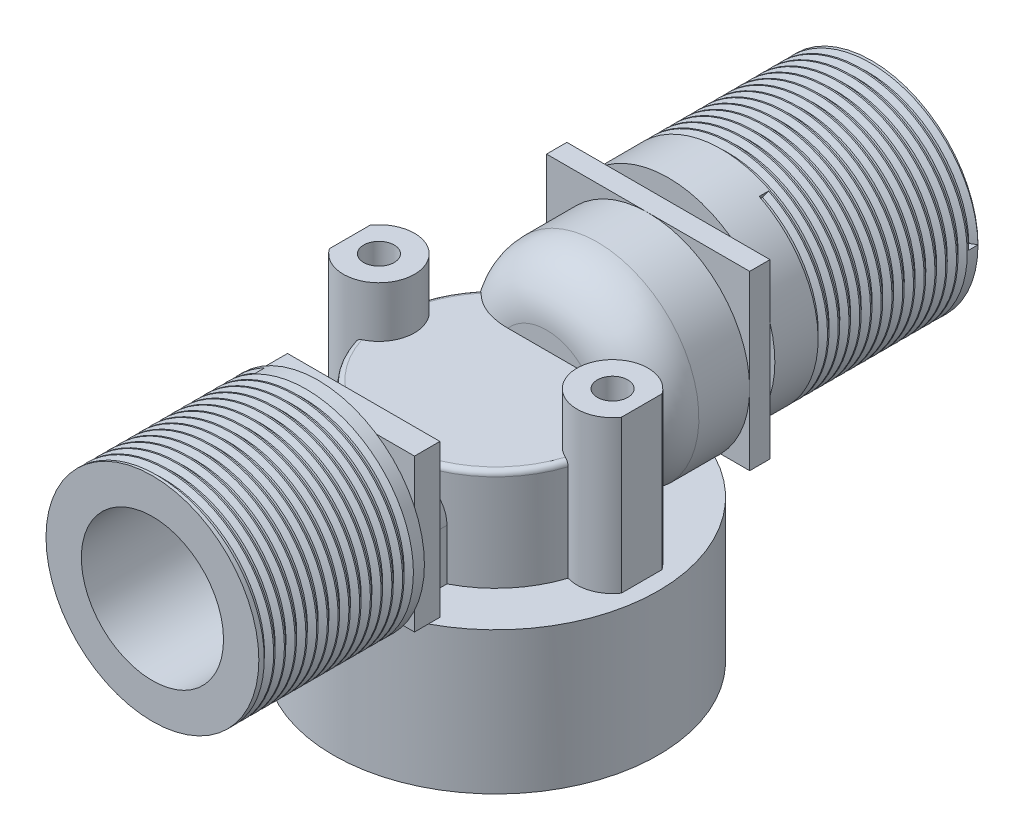
SolidWorks part; units mm, degrees
ref_plane "Спереди" through (0, 0, 0) normal (0, 0, 1) x (1, 0, 0)
ref_plane "Сверху" through (0, 0, 0) normal (0, 1, 0) x (1, 0, 0)
ref_plane "Справа" through (0, 0, 0) normal (1, 0, 0) x (0, 0, -1)
sketch "Эскиз1" plane through (0, 0, 0) normal (0, 1, 0) x (1, 0, 0)
  circle A0 centre (0, 0) radius 16
  dimension "D1" = 32
extrude "Бобышка-Вытянуть1" add sketch "Эскиз1" along normal blind 14
sketch "Эскиз2" plane through (0, 14, 0) normal (0, 1, 0) x (1, 0, 0)
  circle A0 centre (0, 0) radius 11
  dimension "D1" = 22
extrude "Бобышка-Вытянуть2" add sketch "Эскиз2" along normal blind 10
sketch "Эскиз3" plane through (0, 14, 0) normal (0, 1, 0) x (1, 0, 0)
  line L0 (0, 13.8685) -> (0, -18.4575) construction
  circle A0 centre (11.5, 0) radius 3.5
  circle A1 centre (-11.5, 0) radius 3.5
extrude "Бобышка-Вытянуть3" add sketch "Эскиз3" along normal blind 15
sketch "Эскиз4" plane through (0, 29, 0) normal (0, 1, 0) x (1, 0, 0)
  line L0 (-14.3723, 2) -> (-14.3723, -2)
  line L1 (0, 11) -> (0, -11) construction
  line L2 (14.3723, 2) -> (14.3723, -2)
  circle A0 centre (-11.5, 0) radius 1.5
  circle A1 centre (11.5, 0) radius 1.5
  arc A2 (-14.3723, 2) -> (-14.3723, -2) centre (-11.5, 0) ccw
  arc A3 (10.4783, 3.3475) -> (-10.4783, 3.3475) centre (0, 0) ccw construction
  arc A4 (-10.4783, -3.3475) -> (10.4783, -3.3475) centre (0, 0) ccw construction
  arc A6 (-14.3723, 2) -> (-14.3723, -2) centre (-11.5, 0) ccw
  arc A9 (14.3723, 2) -> (14.3723, -2) centre (11.5, 0) cw
  circle M1 centre (-11.5, 0) radius 3.5
  dimension "D1" = 4
extrude "Вырез-Вытянуть1" cut sketch "Эскиз4" against normal blind 15 contours L0 M1 | A0 | A1 | A9 L2 region at (-14.6254, 29, 0) region at (14.6254, 29, 0) region at (-11.5, 29, 0) region at (11.5, 29, 0)
sketch "Эскиз5" plane through (0, 0, 0) normal (0, 0, 1) x (1, 0, 0)
  line L0 (10.4783, 24) -> (-10.4783, 24) construction
  line L1 (-5, 19) -> (-5, 14)
  line L2 (-5, 14) -> (5, 14)
  line L3 (5, 14) -> (5, 19)
  arc A0 (5, 19) -> (-5, 19) centre (0, 19) ccw
  dimension "D1" = 10
extrude "Бобышка-Вытянуть8" add sketch "Эскиз5" along normal blind 13
sketch "Эскиз6" plane through (0, 0, 13) normal (0, 0, 1) x (1, 0, 0)
  line L1 (16, 14) -> (-16, 14) construction
  line L2 (-7.5, 29) -> (7.5, 29)
  line L3 (7.5, 29) -> (7.5, 14)
  line L4 (7.5, 14) -> (-7.5, 14)
  line L5 (-7.5, 14) -> (-7.5, 29)
  dimension "D1" = 15
  dimension "D2" = 15
extrude "Бобышка-Вытянуть9" add sketch "Эскиз6" along normal blind 2.5
sketch "Эскиз7" plane through (0, 0, 15.5) normal (0, 0, 1) x (1, 0, 0)
  line L0 (7.5, 29) -> (-7.5, 29) construction
  circle A0 centre (0, 22.25) radius 6.5
  dimension "D1" = 6.75
extrude "Бобышка-Вытянуть10" add sketch "Эскиз7" along normal blind 2
sketch "Эскиз41" plane through (0, 0, 17.5) normal (0, 0, 1) x (1, 0, 0)
  circle A0 centre (0, 22.25) radius 10.4775
  dimension "D1" = 20.955
extrude "Бобышка-Вытянуть19" add sketch "Эскиз41" along normal blind 16.3
ref_plane "Плоскость1" through (0, 0, -17) normal (0, 0, 1) x (1, 0, 0)
sketch "Эскиз35" plane through (0, 0, -17) normal (0, 0, 1) x (1, 0, 0)
  line L0 (-10, 30.75) -> (10, 30.75)
  line L1 (10, 30.75) -> (10, 13.75)
  line L2 (10, 13.75) -> (-10, 13.75)
  line L3 (-10, 13.75) -> (-10, 30.75)
  dimension "D1" = 17
  dimension "D2" = 20
extrude "Бобышка-Вытянуть17" add sketch "Эскиз35" along normal blind 2
sketch "Эскиз36" plane through (0, 0, -15) normal (0, 0, 1) x (1, 0, 0)
  circle A0 centre (0, 20.75) radius 10
  dimension "D1" = 20
extrude "Бобышка-Вытянуть18" add sketch "Эскиз36" along normal blind 10
fillet "Скругление1" radius 5 1 edges at (0, 30.75, -5)
sketch "Эскиз40" plane through (0, 0, 0) normal (0, -1, 0) x (1, 0, 0)
  line L0 (-7.6613, 0) -> (6.2158, 0)
  line L1 (0, 0) -> (0, 8.1557)
sketch "Эскиз42" plane through (0, 0, -17) normal (0, 0, -1) x (-1, 0, 0)
  circle A0 centre (0, 22.25) radius 10.4775
  dimension "D1" = 20.955
extrude "Бобышка-Вытянуть20" add sketch "Эскиз42" along normal blind 20
fillet "Скругление2" radius 0.5 4 edges at (-6.4876, 24, 8.8832) (6.4876, 24, 8.8832) (-9.6382, 24, -5.3014) (9.6382, 24, -5.3014)
thread "Резьба1" pitch 1.0583 method cut profile "Профиль резьбы1" start angle 0, offset 0, length 15, pitch 1.0583, diameter 20.955
ref_plane "Плоскость2" through (-10.4775, 22.25, 33.8) normal (0, -1, 0) x (-1, 0, 0)
sketch "Профиль резьбы1" plane through (-10.4775, 22.25, 33.8) normal (0, -1, 0) x (-1, 0, 0)
  line L0 (0, 0) -> (0, 1.0583) construction
  line L11 (0, 0) -> (0, 0.926)
  line L12 (0, 0.926) -> (-0.5728, 0.5953)
  line L13 (-0.5728, 0.5953) -> (-0.5728, 0.3307)
  line L15 (-0.5728, 0.3307) -> (0, 0)
  line L17 (-0.5728, 0.463) -> (0, 0.463) construction
  point P2 (0, 0)
  dimension "Pitch" = 1.0583
  dimension "Profile_Angle" = 60
  dimension "Profile_Land" = 0.2646
  dimension "Profile_Height" = 0.5728
thread "Резьба2" pitch 1.0583 method cut profile "Профиль резьбы2" start angle 0, offset 0, length 15, pitch 1.0583, diameter 20.955
ref_plane "Плоскость3" through (10.4775, 22.25, -37) normal (0, -1, 0) x (1, 0, 0)
sketch "Профиль резьбы2" plane through (10.4775, 22.25, -37) normal (0, -1, 0) x (1, 0, 0)
  line L0 (0, 0) -> (0, 1.0583) construction
  line L11 (0, 0) -> (0, 0.926)
  line L12 (0, 0.926) -> (-0.5728, 0.5953)
  line L13 (-0.5728, 0.5953) -> (-0.5728, 0.3307)
  line L15 (-0.5728, 0.3307) -> (0, 0)
  line L17 (-0.5728, 0.463) -> (0, 0.463) construction
  point P2 (0, 0)
  dimension "Pitch" = 1.0583
  dimension "Profile_Angle" = 60
  dimension "Profile_Land" = 0.2646
  dimension "Profile_Height" = 0.5728
sketch "Эскиз52" plane through (0, 0, 33.8) normal (0, 0, 1) x (1, 0, 0)
  circle A0 centre (0, 22.25) radius 7
  dimension "D1" = 14
extrude "Вырез-Вытянуть2" cut sketch "Эскиз52" against normal blind 15
sketch "Эскиз53" plane through (0, 0, -37) normal (0, 0, -1) x (-1, 0, 0)
  circle A0 centre (0, 22.25) radius 7
  dimension "D1" = 14
extrude "Вырез-Вытянуть3" cut sketch "Эскиз53" against normal blind 25
